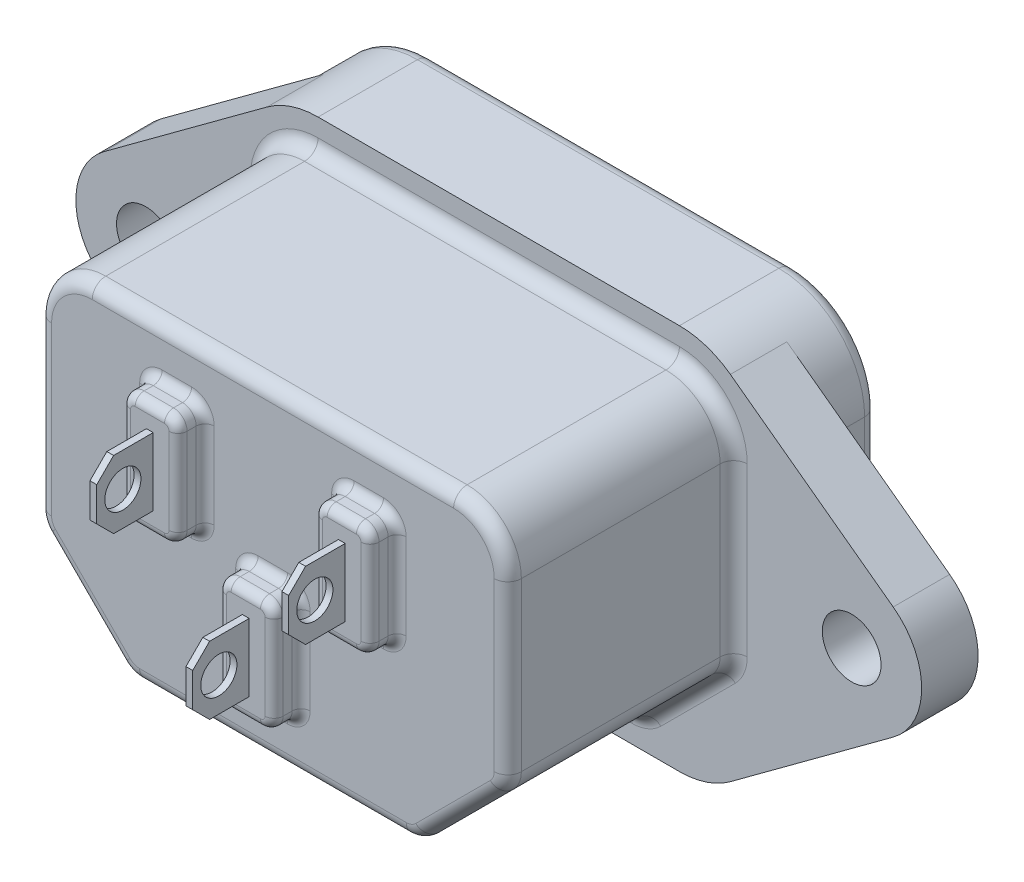
SolidWorks part; units mm, degrees
material "PW50:30:C1:0:1:2:Re:16:"
ref_plane "Front" through (0, 0, 0) normal (0, 0, 1) x (1, 0, 0)
ref_plane "Top" through (0, 0, 0) normal (0, 1, 0) x (1, 0, 0)
ref_plane "Side" through (0, 0, 0) normal (1, 0, 0) x (0, 0, -1)
sketch "Sketch1" plane through (0, 0, 0) normal (0, 0, 1) x (1, 0, 0)
  line L8 (-54.229, 34.671) -> (-33.909, 34.671)
  line L9 (-59.055, 17.78) -> (-59.055, 29.845)
  line L10 (-54.229, 12.954) -> (-33.909, 12.954)
  line L11 (-29.083, 17.78) -> (-29.083, 29.845)
  arc A8 (-54.229, 34.671) -> (-59.055, 29.845) centre (-54.229, 29.845) ccw
  arc A9 (-59.055, 17.78) -> (-54.229, 12.954) centre (-54.229, 17.78) ccw
  arc A10 (-33.909, 12.954) -> (-29.083, 17.78) centre (-33.909, 17.78) ccw
  arc A11 (-29.083, 29.845) -> (-33.909, 34.671) centre (-33.909, 29.845) ccw
extrude "Base-Extrude" add sketch "Sketch1" against normal blind 3.175
sketch "Sketch2" plane through (0, 0, 0) normal (0, 0, 1) x (1, 0, 0)
  line L2 (-54.229, 12.954) -> (-33.909, 12.954)
  line L3 (-54.229, 34.671) -> (-33.909, 34.671)
  line L4 (-57.0922, 33.7299) -> (-66.2485, 26.9818)
  line L5 (-66.2485, 20.6432) -> (-57.0922, 13.8951)
  line L6 (-31.0458, 13.8951) -> (-21.8895, 20.6432)
  line L7 (-31.0458, 33.7299) -> (-21.8895, 26.9818)
  arc A4 (-66.2485, 26.9818) -> (-66.2485, 20.6432) centre (-63.9128, 23.8125) ccw
  arc A5 (-21.8895, 20.6432) -> (-21.8895, 26.9818) centre (-24.2252, 23.8125) ccw
  circle A7 centre (-63.9128, 23.8125) radius 1.651
  circle A8 centre (-24.2252, 23.8125) radius 1.651
  arc A13 (-33.909, 12.954) -> (-31.0458, 13.8951) centre (-33.909, 17.78) ccw
  arc A14 (-57.0922, 13.8951) -> (-54.229, 12.954) centre (-54.229, 17.78) ccw
  arc A15 (-54.229, 34.671) -> (-57.0922, 33.7299) centre (-54.229, 29.845) ccw
  arc A16 (-31.0458, 33.7299) -> (-33.909, 34.671) centre (-33.909, 29.845) ccw
extrude "Boss-Extrude1" add sketch "Sketch2" along normal blind 3.175
sketch "Sketch3" plane through (0, 0, 3.175) normal (0, 0, 1) x (1, 0, 0)
  line L0 (-30.861, 19.812) -> (-35.941, 14.732)
  line L1 (-57.277, 19.812) -> (-52.197, 14.732)
  line L4 (-54.229, 32.893) -> (-33.909, 32.893)
  line L5 (-30.861, 29.845) -> (-30.861, 17.78)
  line L6 (-33.909, 14.732) -> (-54.229, 14.732)
  line L7 (-57.277, 17.78) -> (-57.277, 29.845)
  line L8 (-54.229, 32.893) -> (-33.909, 32.893)
  line L9 (-30.861, 29.845) -> (-30.861, 19.812)
  line L10 (-35.941, 14.732) -> (-52.197, 14.732)
  line L11 (-57.277, 19.812) -> (-57.277, 29.845)
  arc A4 (-54.229, 32.893) -> (-57.277, 29.845) centre (-54.229, 29.845) ccw
  arc A5 (-30.861, 29.845) -> (-33.909, 32.893) centre (-33.909, 29.845) ccw
  arc A6 (-33.909, 14.732) -> (-30.861, 17.78) centre (-33.909, 17.78) ccw
  arc A7 (-57.277, 17.78) -> (-54.229, 14.732) centre (-54.229, 17.78) ccw
  arc A8 (-54.229, 32.893) -> (-57.277, 29.845) centre (-54.229, 29.845) ccw
  arc A9 (-30.861, 29.845) -> (-33.909, 32.893) centre (-33.909, 29.845) ccw
  dimension "D2" = 45
  dimension "D3" = 45
  dimension "D4" = 5.08
  dimension "D1" = 1.778
extrude "Boss-Extrude2" add sketch "Sketch3" along normal blind 12.7
fillet "Fillet1" radius 1.524 4 edges at (-30.861, 19.812, 9.525) (-35.941, 14.732, 9.525) (-52.197, 14.732, 9.525) (-57.277, 19.812, 9.525)
fillet "Fillet2" radius 0.762 12 edges at (-54.737, 17.272, 3.175) (-57.161, 19.8601, 3.175) (-52.1489, 14.848, 3.175) (-57.277, 25.1441, 3.175) (-44.069, 14.732, 3.175) (-56.3843, 32.0003, 3.175) (-35.9891, 14.848, 3.175) (-44.069, 32.893, 3.175) (-33.401, 17.272, 3.175) (-31.7537, 32.0003, 3.175) (-30.977, 19.8601, 3.175) (-30.861, 25.1441, 3.175)
fillet "Fillet3" radius 0.762 20 edges at (-52.1489, 14.848, 15.875) (-44.069, 14.732, 15.875) (-54.737, 17.272, 15.875) (-35.9891, 14.848, 15.875) (-57.161, 19.8601, 15.875) (-57.6415, 14.3675, -3.175) (-33.401, 17.272, 15.875) (-57.277, 25.1441, 15.875) (-44.069, 12.954, -3.175) (-59.055, 23.8125, -3.175) (-30.977, 19.8601, 15.875) (-56.3843, 32.0003, 15.875) (-30.4965, 14.3675, -3.175) (-57.6415, 33.2575, -3.175) (-30.861, 25.1441, 15.875) (-44.069, 32.893, 15.875) (-29.083, 23.8125, -3.175) (-44.069, 34.671, -3.175) (-31.7537, 32.0003, 15.875) (-30.4965, 33.2575, -3.175)
sketch "Sketch4" plane through (0, 0, -3.175) normal (0, 0, -1) x (-1, 0, 0)
  line L6 (55.499, 20.5485) -> (51.4605, 16.51)
  line L7 (51.4605, 16.51) -> (36.6775, 16.51)
  line L8 (36.6775, 16.51) -> (32.639, 20.5485)
  line L9 (32.639, 20.5485) -> (32.639, 29.845)
  line L10 (33.909, 31.115) -> (54.229, 31.115)
  line L11 (55.499, 29.845) -> (55.499, 20.5485)
  line L12 (55.499, 20.5485) -> (51.4605, 16.51)
  line L13 (51.4605, 16.51) -> (36.6775, 16.51)
  line L14 (36.6775, 16.51) -> (32.639, 20.5485)
  line L15 (32.639, 20.5485) -> (32.639, 29.845)
  line L16 (33.909, 31.115) -> (54.229, 31.115)
  line L17 (55.499, 29.845) -> (55.499, 20.5485)
  arc A6 (33.909, 31.115) -> (32.639, 29.845) centre (33.909, 29.845) ccw
  arc A7 (55.499, 29.845) -> (54.229, 31.115) centre (54.229, 29.845) ccw
  arc A8 (33.909, 31.115) -> (32.639, 29.845) centre (33.909, 29.845) ccw
  arc A9 (55.499, 29.845) -> (54.229, 31.115) centre (54.229, 29.845) ccw
  dimension "D1" = 1.016
extrude "Cut-Extrude1" cut sketch "Sketch4" against normal blind 16.891
fillet "Fillet4" radius 0.762 12 edges at (-32.639, 20.5485, 5.2705) (-36.6775, 16.51, 5.2705) (-51.4605, 16.51, 5.2705) (-55.499, 20.5485, 5.2705) (-55.499, 25.1967, 13.716) (-53.4798, 18.5292, 13.716) (-44.069, 16.51, 13.716) (-34.6582, 18.5292, 13.716) (-55.127, 30.743, 13.716) (-44.069, 31.115, 13.716) (-33.011, 30.743, 13.716) (-32.639, 25.1967, 13.716)
fillet "Fillet5" radius 0.762 12 edges at (-44.069, 16.51, -3.175) (-36.7015, 16.568, -3.175) (-51.4365, 16.568, -3.175) (-34.6582, 18.5292, -3.175) (-53.4798, 18.5292, -3.175) (-32.697, 20.5725, -3.175) (-55.441, 20.5725, -3.175) (-32.639, 25.3546, -3.175) (-55.499, 25.3546, -3.175) (-33.011, 30.743, -3.175) (-55.127, 30.743, -3.175) (-44.069, 31.115, -3.175)
sketch "Sketch5" plane through (0, 0, 15.875) normal (0, 0, 1) x (1, 0, 0)
  line L0 (-44.069, 34.671) -> (-44.069, 12.954) construction
  line L2 (-50.292, 30.1625) -> (-48.641, 30.1625)
  line L3 (-51.054, 29.4005) -> (-51.054, 24.5745)
  line L4 (-48.641, 23.8125) -> (-50.292, 23.8125)
  line L5 (-47.879, 24.5745) -> (-47.879, 29.4005)
  line L6 (-37.846, 30.1625) -> (-39.497, 30.1625)
  line L7 (-37.084, 29.4005) -> (-37.084, 24.5745)
  line L8 (-39.497, 23.8125) -> (-37.846, 23.8125)
  line L9 (-40.259, 24.5745) -> (-40.259, 29.4005)
  line L10 (-43.2435, 23.8125) -> (-44.8945, 23.8125)
  line L11 (-45.6565, 23.0505) -> (-45.6565, 18.2245)
  line L12 (-42.4815, 23.0505) -> (-42.4815, 18.2245)
  line L13 (-44.8945, 17.4625) -> (-43.2435, 17.4625)
  line L15 (-54.229, 34.671) -> (-33.909, 34.671) construction
  line L16 (-54.229, 12.954) -> (-33.909, 12.954) construction
  arc A0 (-43.2435, 17.4625) -> (-42.4815, 18.2245) centre (-43.2435, 18.2245) ccw
  arc A1 (-44.8945, 17.4625) -> (-45.6565, 18.2245) centre (-44.8945, 18.2245) cw
  arc A2 (-43.2435, 23.8125) -> (-42.4815, 23.0505) centre (-43.2435, 23.0505) cw
  arc A3 (-45.6565, 23.0505) -> (-44.8945, 23.8125) centre (-44.8945, 23.0505) cw
  arc A4 (-47.879, 24.5745) -> (-48.641, 23.8125) centre (-48.641, 24.5745) cw
  arc A5 (-50.292, 23.8125) -> (-51.054, 24.5745) centre (-50.292, 24.5745) cw
  arc A6 (-47.879, 29.4005) -> (-48.641, 30.1625) centre (-48.641, 29.4005) ccw
  arc A7 (-51.054, 29.4005) -> (-50.292, 30.1625) centre (-50.292, 29.4005) cw
  arc A8 (-40.259, 24.5745) -> (-39.497, 23.8125) centre (-39.497, 24.5745) ccw
  arc A9 (-37.846, 23.8125) -> (-37.084, 24.5745) centre (-37.846, 24.5745) ccw
  arc A10 (-37.084, 29.4005) -> (-37.846, 30.1625) centre (-37.846, 29.4005) ccw
  arc A11 (-40.259, 29.4005) -> (-39.497, 30.1625) centre (-39.497, 29.4005) cw
  point P15 (-44.069, 23.8125)
  point P18 (-44.069, 17.2085)
  point P22 (-42.4815, 17.2085)
  point P27 (-42.4815, 23.8125)
  point P32 (-47.879, 23.8125)
  point P35 (-51.054, 23.8125)
  point P38 (-47.879, 28.8925)
  point P41 (-51.054, 28.8925)
  dimension "D3" = 0.762
  dimension "D1" = 3.175
  dimension "D2" = 6.35
extrude "Boss-Extrude3" add sketch "Sketch5" along normal blind 1.524
fillet "Fillet6" radius 0.508 48 edges at (-51.054, 26.9875, 15.875) (-51.054, 26.9875, 17.399) (-45.6565, 20.6375, 15.875) (-45.6565, 20.6375, 17.399) (-40.259, 26.9875, 15.875) (-40.259, 26.9875, 17.399) (-50.8308, 24.0357, 15.875) (-50.8308, 29.9393, 15.875) (-50.8308, 24.0357, 17.399) (-50.8308, 29.9393, 17.399) (-45.4333, 23.5893, 15.875) (-45.4333, 17.6857, 15.875) (-45.4333, 23.5893, 17.399) (-45.4333, 17.6857, 17.399) (-40.0358, 29.9393, 15.875) (-40.0358, 24.0357, 15.875) (-40.0358, 29.9393, 17.399) (-40.0358, 24.0357, 17.399) (-49.4665, 23.8125, 15.875) (-49.4665, 30.1625, 15.875) (-49.4665, 23.8125, 17.399) (-49.4665, 30.1625, 17.399) (-44.069, 23.8125, 15.875) (-44.069, 17.4625, 15.875) (-44.069, 23.8125, 17.399) (-44.069, 17.4625, 17.399) (-38.6715, 30.1625, 15.875) (-38.6715, 23.8125, 15.875) (-38.6715, 30.1625, 17.399) (-38.6715, 23.8125, 17.399) (-48.1022, 24.0357, 15.875) (-48.1022, 29.9393, 15.875) (-48.1022, 24.0357, 17.399) (-48.1022, 29.9393, 17.399) (-42.7047, 23.5893, 15.875) (-42.7047, 17.6857, 15.875) (-42.7047, 23.5893, 17.399) (-42.7047, 17.6857, 17.399) (-37.3072, 29.9393, 15.875) (-37.3072, 24.0357, 15.875) (-37.3072, 29.9393, 17.399) (-37.3072, 24.0357, 17.399) (-47.879, 26.9875, 15.875) (-47.879, 26.9875, 17.399) (-42.4815, 20.6375, 15.875) (-42.4815, 20.6375, 17.399) (-37.084, 26.9875, 15.875) (-37.084, 26.9875, 17.399)
sketch "Sketch6" plane through (0, 0, 17.399) normal (0, 0, 1) x (1, 0, 0)
  line L0 (-44.069, 34.671) -> (-44.069, 12.954) construction
  line L1 (-54.229, 34.671) -> (-33.909, 34.671) construction
  line L2 (-54.229, 12.954) -> (-33.909, 12.954) construction
  line L3 (-39.624, 28.8925) -> (-37.719, 28.8925)
  line L4 (-39.624, 28.8925) -> (-39.624, 25.0825)
  line L5 (-37.719, 25.0825) -> (-39.624, 25.0825)
  line L6 (-37.719, 25.0825) -> (-37.719, 28.8925)
  line L7 (-48.514, 28.8925) -> (-50.419, 28.8925)
  line L8 (-48.514, 28.8925) -> (-48.514, 25.0825)
  line L9 (-50.419, 25.0825) -> (-48.514, 25.0825)
  line L10 (-50.419, 25.0825) -> (-50.419, 28.8925)
  line L11 (-43.1165, 22.5425) -> (-45.0215, 22.5425)
  line L12 (-45.0215, 22.5425) -> (-45.0215, 18.7325)
  line L13 (-43.1165, 22.5425) -> (-43.1165, 18.7325)
  line L14 (-45.0215, 18.7325) -> (-43.1165, 18.7325)
  line L15 (-39.497, 30.1625) -> (-37.846, 30.1625) construction
  line L16 (-44.8945, 23.8125) -> (-43.2435, 23.8125) construction
  line L17 (-40.259, 24.5745) -> (-40.259, 29.4005) construction
  point P17 (-44.069, 22.5425)
  point P20 (-44.069, 18.7325)
  dimension "D1" = 3.81
  dimension "D2" = 1.905
  dimension "D3" = 1.27
  dimension "D4" = 1.27
  dimension "D5" = 0.635
extrude "Boss-Extrude4" add sketch "Sketch6" along normal blind 3.175 and the other way offset from surface 1.524 other way up to face at (-44.069, 22.4307, -3.175)
sketch "Sketch7" plane through (0, 0, 20.574) normal (0, 0, 1) x (1, 0, 0)
  line L0 (-43.8785, 17.9705) -> (-43.2435, 17.9705)
  line L1 (-38.862, 28.8925) -> (-38.862, 25.0825)
  line L2 (-38.862, 29.6545) -> (-38.862, 24.3205)
  line L3 (-49.657, 25.0825) -> (-49.657, 28.8925)
  line L4 (-49.657, 24.3205) -> (-49.657, 29.6545)
  line L5 (-44.2595, 22.5425) -> (-44.2595, 18.7325)
  line L6 (-44.2595, 23.3045) -> (-44.2595, 17.9705)
  line L7 (-43.8785, 22.5425) -> (-43.8785, 18.7325)
  line L8 (-43.8785, 23.3045) -> (-43.8785, 17.9705)
  line L9 (-38.481, 25.0825) -> (-38.481, 28.8925)
  line L10 (-38.481, 24.3205) -> (-38.481, 29.6545)
  line L11 (-49.276, 28.8925) -> (-49.276, 25.0825)
  line L12 (-49.276, 29.6545) -> (-49.276, 24.3205)
  line L13 (-44.2595, 23.3045) -> (-44.8945, 23.3045)
  line L14 (-38.862, 29.6545) -> (-39.497, 29.6545)
  line L15 (-38.481, 24.3205) -> (-37.846, 24.3205)
  line L16 (-45.1485, 23.0505) -> (-45.1485, 18.2245)
  line L17 (-44.8945, 17.9705) -> (-43.2435, 17.9705)
  line L18 (-42.9895, 18.2245) -> (-42.9895, 23.0505)
  line L19 (-43.2435, 23.3045) -> (-44.8945, 23.3045)
  line L20 (-45.1485, 23.0505) -> (-45.1485, 18.2245)
  line L21 (-44.8945, 17.9705) -> (-44.2595, 17.9705)
  line L22 (-42.9895, 18.2245) -> (-42.9895, 23.0505)
  line L23 (-43.2435, 23.3045) -> (-43.8785, 23.3045)
  line L24 (-39.751, 29.4005) -> (-39.751, 24.5745)
  line L25 (-39.497, 24.3205) -> (-37.846, 24.3205)
  line L26 (-37.592, 24.5745) -> (-37.592, 29.4005)
  line L27 (-37.846, 29.6545) -> (-39.497, 29.6545)
  line L28 (-39.751, 29.4005) -> (-39.751, 24.5745)
  line L29 (-39.497, 24.3205) -> (-38.862, 24.3205)
  line L30 (-37.592, 24.5745) -> (-37.592, 29.4005)
  line L31 (-37.846, 29.6545) -> (-38.481, 29.6545)
  line L32 (-50.546, 29.4005) -> (-50.546, 24.5745)
  line L33 (-50.292, 24.3205) -> (-48.641, 24.3205)
  line L34 (-48.387, 24.5745) -> (-48.387, 29.4005)
  line L35 (-48.641, 29.6545) -> (-50.292, 29.6545)
  line L36 (-50.546, 29.4005) -> (-50.546, 24.5745)
  line L37 (-50.292, 24.3205) -> (-49.657, 24.3205)
  line L38 (-48.387, 24.5745) -> (-48.387, 29.4005)
  line L39 (-48.641, 29.6545) -> (-49.276, 29.6545)
  line L40 (-49.657, 29.6545) -> (-50.292, 29.6545)
  line L41 (-49.276, 24.3205) -> (-48.641, 24.3205)
  arc A4 (-44.8945, 23.3045) -> (-45.1485, 23.0505) centre (-44.8945, 23.0505) ccw
  arc A5 (-45.1485, 18.2245) -> (-44.8945, 17.9705) centre (-44.8945, 18.2245) ccw
  arc A6 (-43.2435, 17.9705) -> (-42.9895, 18.2245) centre (-43.2435, 18.2245) ccw
  arc A7 (-42.9895, 23.0505) -> (-43.2435, 23.3045) centre (-43.2435, 23.0505) ccw
  arc A8 (-44.8945, 23.3045) -> (-45.1485, 23.0505) centre (-44.8945, 23.0505) ccw
  arc A9 (-45.1485, 18.2245) -> (-44.8945, 17.9705) centre (-44.8945, 18.2245) ccw
  arc A10 (-43.2435, 17.9705) -> (-42.9895, 18.2245) centre (-43.2435, 18.2245) ccw
  arc A11 (-42.9895, 23.0505) -> (-43.2435, 23.3045) centre (-43.2435, 23.0505) ccw
  arc A12 (-39.497, 29.6545) -> (-39.751, 29.4005) centre (-39.497, 29.4005) ccw
  arc A13 (-39.751, 24.5745) -> (-39.497, 24.3205) centre (-39.497, 24.5745) ccw
  arc A14 (-37.846, 24.3205) -> (-37.592, 24.5745) centre (-37.846, 24.5745) ccw
  arc A15 (-37.592, 29.4005) -> (-37.846, 29.6545) centre (-37.846, 29.4005) ccw
  arc A16 (-39.497, 29.6545) -> (-39.751, 29.4005) centre (-39.497, 29.4005) ccw
  arc A17 (-39.751, 24.5745) -> (-39.497, 24.3205) centre (-39.497, 24.5745) ccw
  arc A18 (-37.846, 24.3205) -> (-37.592, 24.5745) centre (-37.846, 24.5745) ccw
  arc A19 (-37.592, 29.4005) -> (-37.846, 29.6545) centre (-37.846, 29.4005) ccw
  arc A20 (-50.292, 29.6545) -> (-50.546, 29.4005) centre (-50.292, 29.4005) ccw
  arc A21 (-50.546, 24.5745) -> (-50.292, 24.3205) centre (-50.292, 24.5745) ccw
  arc A22 (-48.641, 24.3205) -> (-48.387, 24.5745) centre (-48.641, 24.5745) ccw
  arc A23 (-48.387, 29.4005) -> (-48.641, 29.6545) centre (-48.641, 29.4005) ccw
  arc A24 (-50.292, 29.6545) -> (-50.546, 29.4005) centre (-50.292, 29.4005) ccw
  arc A25 (-50.546, 24.5745) -> (-50.292, 24.3205) centre (-50.292, 24.5745) ccw
  arc A26 (-48.641, 24.3205) -> (-48.387, 24.5745) centre (-48.641, 24.5745) ccw
  arc A27 (-48.387, 29.4005) -> (-48.641, 29.6545) centre (-48.641, 29.4005) ccw
  dimension "D1" = 0.762
  dimension "D2" = 0.762
  dimension "D3" = 0.762
  dimension "D4" = 0.762
  dimension "D5" = 0.762
  dimension "D6" = 0.762
  dimension "D7" = 0
  dimension "D8" = 0
  dimension "D9" = 0
extrude "Cut-Extrude2" cut sketch "Sketch7" against normal up to surface (3.175 mm away) up to face at (-38.6715, 26.9875, 17.399)
sketch "Sketch8" plane through (-38.481, 0, 0) normal (1, 0, 0) x (0, 0, -1)
  line L1 (-20.574, 28.8925) -> (-17.399, 28.8925) construction
  line L2 (-20.574, 22.5425) -> (-17.399, 22.5425) construction
  line L3 (-17.399, 24.3205) -> (-21.336, 24.3205)
  line L4 (-21.336, 24.3205) -> (-21.336, 29.6545)
  line L5 (-21.336, 29.6545) -> (-17.399, 29.6545)
  line L6 (-17.399, 24.3205) -> (-21.336, 24.3205)
  line L7 (-21.336, 24.3205) -> (-21.336, 29.6545)
  line L8 (-21.336, 29.6545) -> (-17.399, 29.6545)
  line L9 (-21.336, 23.3045) -> (-17.399, 23.3045)
  line L10 (-17.399, 17.9705) -> (-21.336, 17.9705)
  line L11 (-21.336, 23.3045) -> (-21.336, 17.9705)
  line L12 (-21.336, 23.3045) -> (-17.399, 23.3045)
  line L13 (-17.399, 17.9705) -> (-21.336, 17.9705)
  line L14 (-21.336, 23.3045) -> (-21.336, 17.9705)
  line L15 (-19.6259, 22.5425) -> (-17.399, 22.5425)
  line L16 (-20.574, 28.8925) -> (-20.574, 25.0825)
  line L17 (-20.574, 25.0825) -> (-17.399, 25.0825)
  line L18 (-17.399, 25.0825) -> (-17.399, 28.8925)
  line L19 (-17.399, 28.8925) -> (-20.574, 28.8925)
  line L20 (-17.399, 25.0825) -> (-20.574, 25.0825) construction
  line L21 (-19.6259, 25.0825) -> (-17.399, 25.0825)
  line L22 (-17.399, 18.7325) -> (-20.574, 18.7325) construction
  line L23 (-17.399, 28.8925) -> (-19.6259, 28.8925)
  line L24 (-17.399, 18.7325) -> (-19.6259, 18.7325)
  line L25 (-20.574, 25.0825) -> (-20.574, 28.8925) construction
  line L26 (-20.574, 22.5425) -> (-20.574, 18.7325) construction
  line L27 (-20.574, 26.0306) -> (-20.574, 27.9444)
  line L28 (-20.574, 21.5944) -> (-20.574, 19.6806)
  line L29 (-19.6259, 28.8925) -> (-20.574, 27.9444)
  line L30 (-20.574, 26.0306) -> (-19.6259, 25.0825)
  line L31 (-19.6259, 22.5425) -> (-20.574, 21.5944)
  line L32 (-20.574, 19.6806) -> (-19.6259, 18.7325)
  line L33 (-20.574, 26.9875) -> (-11.5559, 26.9875) construction
  line L34 (-20.574, 20.6375) -> (-10.3574, 20.6375) construction
  line L35 (-17.399, 28.8925) -> (-17.399, 29.6545)
  line L36 (-17.399, 25.0825) -> (-17.399, 24.3205)
  line L37 (-17.399, 23.3045) -> (-17.399, 22.5425)
  line L38 (-17.399, 18.7325) -> (-17.399, 17.9705)
  circle A0 centre (-19.1066, 26.9875) radius 1.016
  circle A1 centre (-19.1066, 20.6375) radius 1.016
  dimension "D9" = 2.032
  dimension "D10" = 1.4674
  dimension "D4" = 45
  dimension "D5" = 45
  dimension "D6" = 45
  dimension "D7" = 45
  dimension "D8" = 0.9481
  dimension "D1" = 0.762
  dimension "D2" = 0.762
  dimension "D3" = 0
extrude "Cut-Extrude3" cut sketch "Sketch8" against normal through all
sketch "Sketch9" plane through (0, 28.8925, 0) normal (0, 1, 0) x (-1, 0, 0)
  line L0 (38.6715, -1.651) -> (38.6715, -3.4299) construction
  line L1 (37.719, -1.651) -> (39.624, -1.651) construction
  line L2 (49.4665, -1.651) -> (49.4665, -3.4299) construction
  line L3 (50.419, -1.651) -> (48.514, -1.651) construction
  line L4 (50.8657, 0.8297) -> (50.6467, 0.8297)
  line L6 (50.6467, 0.8297) -> (49.4665, -2.413)
  line L7 (37.2723, 0.8297) -> (37.2723, -2.7869)
  line L8 (37.2723, -2.7869) -> (50.8657, -2.7869)
  line L9 (45.2492, 0.8297) -> (44.069, -2.413)
  line L10 (39.8517, 0.8297) -> (38.6715, -2.413)
  line L11 (50.8657, -2.7869) -> (50.8657, 0.8297)
  line L12 (37.4913, 0.8297) -> (38.6715, -2.413)
  line L13 (37.4913, 0.8297) -> (37.2723, 0.8297)
  line L14 (42.8888, 0.8297) -> (44.069, -2.413)
  line L15 (42.8888, 0.8297) -> (39.8517, 0.8297)
  line L16 (48.2863, 0.8297) -> (49.4665, -2.413)
  line L17 (44.069, 15.113) -> (44.069, -9.2844) construction
  line L18 (48.2863, 0.8297) -> (45.2492, 0.8297)
  line L19 (45.0215, 13.716) -> (45.0215, -1.651) construction
  line L20 (43.1165, 13.716) -> (43.1165, -1.651) construction
  line L21 (33.909, -2.413) -> (54.229, -2.413) construction
  line L22 (54.229, 15.113) -> (33.909, 15.113) construction
  line L23 (45.0215, -1.651) -> (43.1165, -1.651) construction
  dimension "D1" = 20
  dimension "D2" = 20
  dimension "D3" = 2.4807
  dimension "D4" = 3.6166
  dimension "D5" = 13.5934
  dimension "D6" = 6.7967
extrude "Cut-Extrude4" cut sketch "Sketch9" against normal up to surface (10.16 mm away) up to face at (-44.069, 18.7325, 6.0325)
